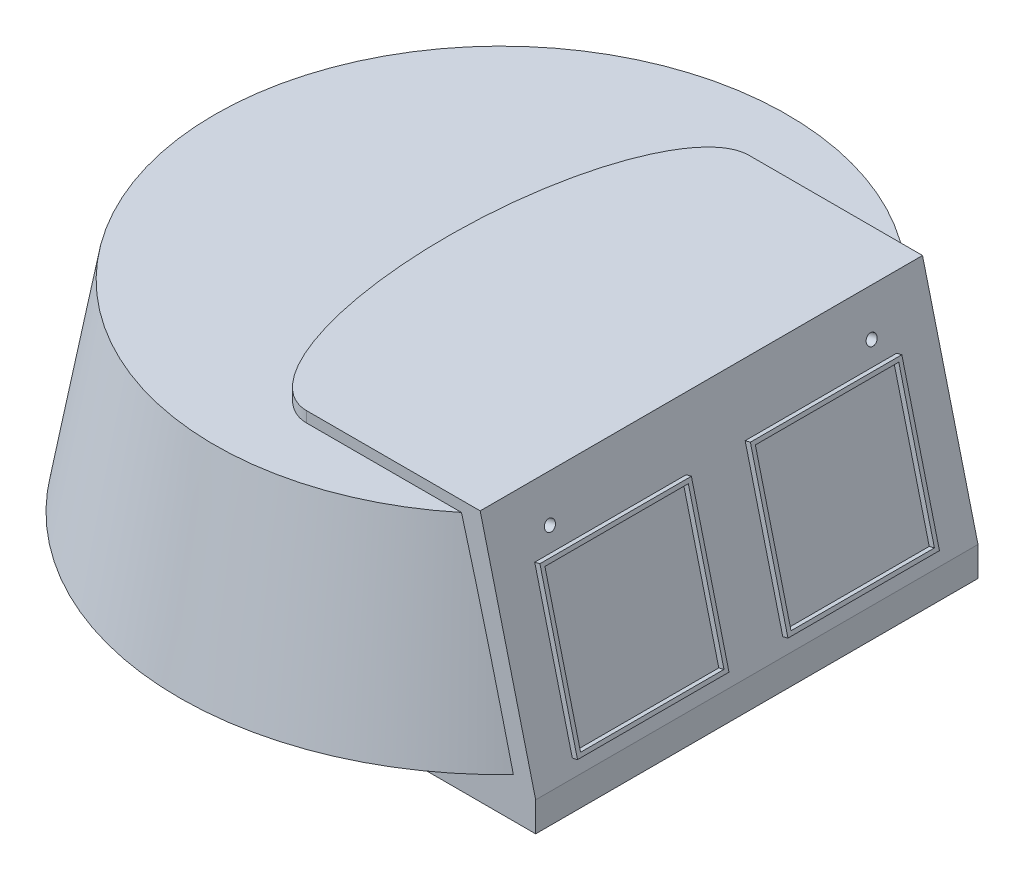
SolidWorks part; units mm, degrees
ref_plane "Front Plane" through (0, 0, 0) normal (0, 0, 1) x (1, 0, 0)
ref_plane "Top Plane" through (0, 0, 0) normal (0, 1, 0) x (1, 0, 0)
ref_plane "Right Plane" through (0, 0, 0) normal (1, 0, 0) x (0, 0, -1)
sketch "Sketch1" plane through (0, 0, 0) normal (0, 0, 1) x (1, 0, 0)
  line L0 (0, 0) -> (240, 0) construction
  line L1 (240, 0) -> (213.551, 150)
  line L2 (213.551, 150) -> (0, 150)
  line L3 (0, 150) -> (0, 0)
  line L4 (0, -30) -> (180, -30)
  line L6 (0, -30) -> (0, 0)
  line L7 (180, -30) -> (193.3569, 0)
  line L8 (193.3569, 0) -> (240, 0)
  dimension "D1" = 240
  dimension "D2" = 80
  dimension "D3" = 150
  dimension "D4" = 30
  dimension "D5" = 66
  dimension "D6" = 180
revolve "Revolve1" add sketch "Sketch1" angle 360 about L3
sketch "Sketch2" plane through (0, 0, 0) normal (0, 0, 1) x (1, 0, 0)
  line L0 (0, 150) -> (0, -30) construction
  line L1 (20, -30) -> (144.5191, -30)
  line L2 (144.5191, -30) -> (249.534, -30)
  line L3 (249.534, -30) -> (249.534, -8)
  line L4 (20, 158) -> (20, -30)
  line L5 (213.551, 150) -> (-213.551, 150) construction
  line L6 (-180, -30) -> (180, -30) construction
  line L11 (198.5521, -8) -> (249.534, -8)
  line L12 (198.5521, -8) -> (249.534, -8) construction
  line L13 (220.2637, 158) -> (-8, 158)
  line L14 (249.534, -8) -> (220.2637, 158)
  line L15 (185.1953, -38) -> (198.5521, -8)
  line L16 (-8, -38) -> (185.1953, -38)
  line L17 (-8, 0) -> (-8, -38)
  line L18 (-8, 158) -> (-8, 0)
  line L19 (220.2637, 158) -> (20, 158)
  line L20 (249.534, -8) -> (220.2637, 158)
  line L23 (188.7571, -30) -> (198.5521, -8) construction
  dimension "D2" = 20
  dimension "D1" = 8
extrude "Boss-Extrude6" add sketch "Sketch2" along normal mid plane 330
sketch "Sketch4" plane through (0, 150, 0) normal (0, 1, 0) x (1, 0, 0)
  line L2 (20, -165) -> (20, 165) construction
  line L3 (220.2637, 165) -> (20, 165) construction
  ellipse E0 centre (20, 0) end of major axis (20, 165) minor radius 60
  dimension "D1" = 60
sketch "Sketch5" plane through (0, 0, 0) normal (0, 0, 1) x (1, 0, 0)
  line L0 (0, -30) -> (0, -60)
  line L1 (-180, -30) -> (71.9375, -30) construction
  line L2 (0, -60) -> (90, -60)
  line L3 (90, -60) -> (105, -30)
  line L5 (105, -30) -> (0, -30)
  dimension "D1" = 90
  dimension "D2" = 105
  dimension "D3" = 30
revolve "Revolve3" add sketch "Sketch5" angle 360 about L0
sketch "Sketch7" plane through (0, 0, 0) normal (0, 0, 1) x (1, 0, 0)
  line L0 (149.534, 158) -> (190.9225, -8)
  line L1 (220.2637, 158) -> (20, 158) construction
  line L2 (71.9375, -30) -> (249.534, -30) construction
  line L3 (190.9225, -8) -> (190.9225, -30)
  line L7 (149.534, 158) -> (249.534, 158)
  line L8 (249.534, 158) -> (249.534, -30)
  line L9 (249.534, -30) -> (190.9225, -30)
  line L11 (249.534, -30) -> (249.534, -8) construction
  line L12 (220.2637, 158) -> (20, 158) construction
  dimension "D1" = 100
  dimension "D2" = 76
extrude "Cut-Extrude3" cut sketch "Sketch7" against normal through all both and the other way through all
shell "Shell1" thickness 10 removed face at (-90, -60, 0)
sketch "Sketch8" plane through (177.8706, 44.3481, 0) normal (0.9703, 0.2419, 0) x (0, 0, -1)
  line L0 (-132, 70) -> (-25, 70)
  line L3 (-132, -40) -> (-132, 70)
  line L4 (-135, 73) -> (-22, 73)
  line L6 (-22, -43) -> (-135, -43)
  line L7 (-135, -43) -> (-135, 73)
  line L8 (0, 70) -> (0, -40) construction
  line L9 (-25, 70) -> (-25, -40)
  line L10 (-22, 73) -> (-22, -43)
  line L11 (-135, 73) -> (138, 73) construction
  line L12 (165, -53.9507) -> (-165, -53.9507) construction
  line L13 (-132, 70) -> (135, 70) construction
  line L14 (-25, -40) -> (-132, -40)
  line L15 (135, -40) -> (-132, -40) construction
  line L16 (138, -43) -> (-135, -43) construction
  line L17 (135, 70) -> (135, -40) construction
  line L18 (138, 73) -> (138, -43) construction
  line L19 (25, -40) -> (132, -40)
  line L20 (22, 73) -> (22, -43)
  line L21 (25, 70) -> (25, -40)
  line L22 (135, -43) -> (135, 73)
  line L23 (22, -43) -> (135, -43)
  line L24 (135, 73) -> (22, 73)
  line L25 (132, -40) -> (132, 70)
  line L26 (132, 70) -> (25, 70)
  point P5 (-42.1635, -43)
  point P17 (0, 0)
  dimension "D1" = 110
  dimension "D2" = 107
  dimension "D3" = 10.9507
  dimension "D5" = 22
  dimension "D6" = 3
  dimension "D4" = 3
extrude "Boss-Extrude5" add sketch "Sketch8" along normal blind 4
extrude "Boss-Extrude7" add sketch "Sketch4" along normal up to surface (8 mm away) contours E0 up to face at (84.767, 158, 0)
sketch "Sketch9" plane through (177.8706, 44.3481, 0) normal (0.9703, 0.2419, 0) x (0, 0, -1)
  line L0 (-22, 73) -> (-135, 73) construction
  circle A0 centre (-120, 88) radius 4
  dimension "D1" = 8
  dimension "D2" = 120
  dimension "D3" = 15
extrude "Cut-Extrude4" cut sketch "Sketch9" against normal blind 10
mirror "Mirror1" about plane through (0, 0, 0) normal (0, 0, 1) of "Cut-Extrude4"
